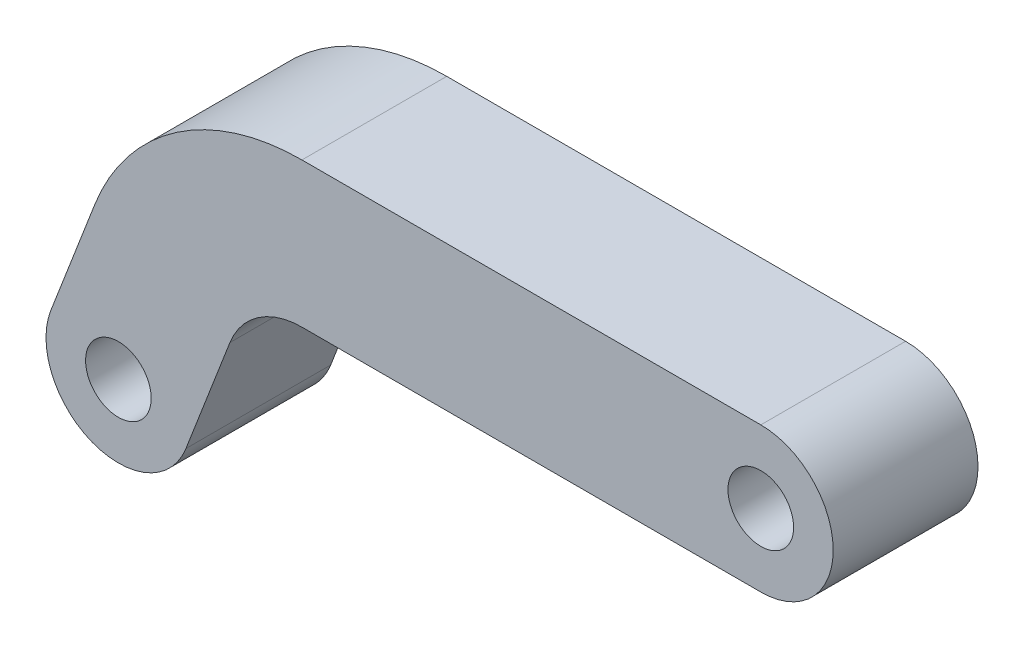
SolidWorks part; units mm, degrees
ref_plane "Front Plane" through (0, 0, 0) normal (0, 0, 1) x (1, 0, 0)
ref_plane "Top Plane" through (0, 0, 0) normal (0, 1, 0) x (1, 0, 0)
ref_plane "Right Plane" through (0, 0, 0) normal (1, 0, 0) x (0, 0, -1)
sketch "Sketch1" plane through (0, 0, 0) normal (0, 0, 1) x (1, 0, 0)
  line L0 (42.2602, 18.542) -> (12.0744, 18.542)
  line L2 (42.2602, 9.017) -> (12.0744, 9.017)
  line L3 (4.4421, -1.7173) -> (7.3361, 5.7687)
  line L4 (-4.4421, 1.7173) -> (-1.5482, 9.2033)
  line L5 (0, 0) -> (42.2602, 13.7795) construction
  circle A0 centre (0, 0) radius 2.159
  circle A1 centre (42.2602, 13.7795) radius 2.159
  arc A2 (42.2602, 9.017) -> (42.2602, 18.542) centre (42.2602, 13.7795) ccw
  arc A4 (-4.4421, 1.7173) -> (4.4421, -1.7173) centre (0, 0) ccw
  arc A5 (12.0744, 9.017) -> (7.3361, 5.7687) centre (12.0744, 3.937) ccw
  arc A6 (12.0744, 18.542) -> (-1.5482, 9.2033) centre (12.0744, 3.937) ccw
  point P9 (12.0744, 3.937)
  point P15 (12.1478, 3.7042)
  point P16 (35.1232, 14.7638)
  point P17 (12.0744, 3.937)
  dimension "D1" = 4.318
  dimension "D4" = 4.7625
  dimension "D5" = 4.7625
  dimension "D6" = 12.7
  dimension "D7" = 5.08
  dimension "D2" = 44.45
extrude "Boss-Extrude1" add sketch "Sketch1" along normal mid plane 9.525
